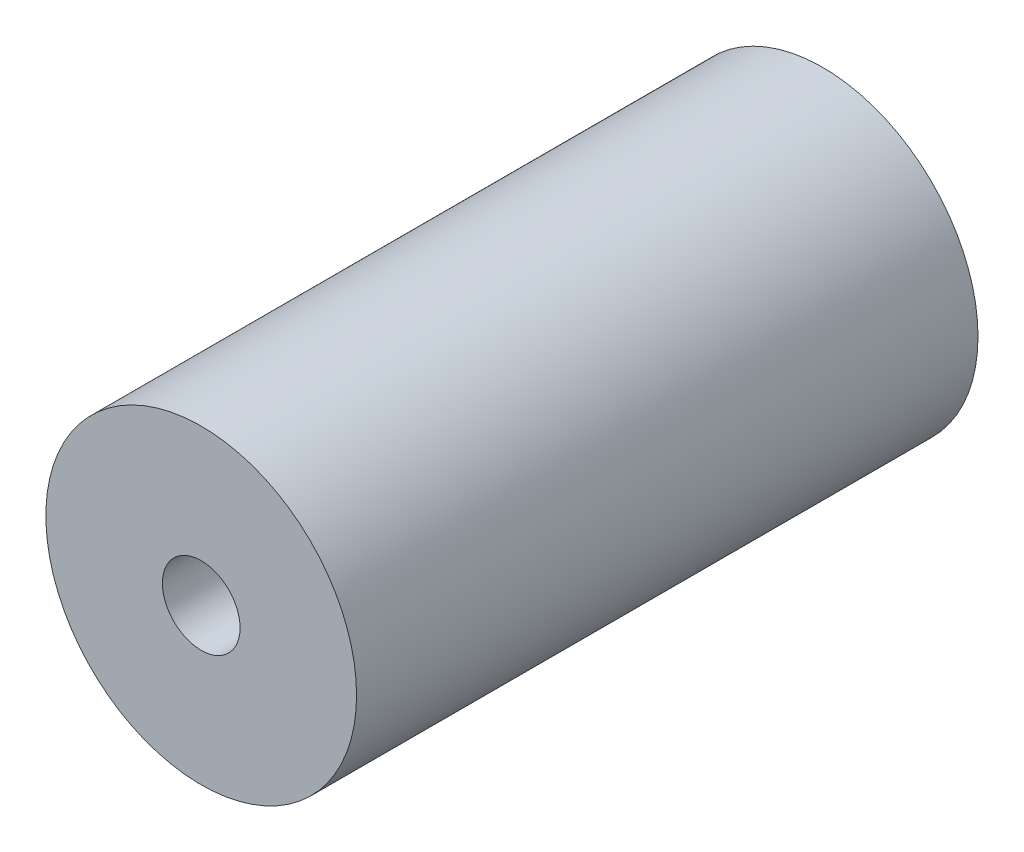
SolidWorks part; units mm, degrees
ref_plane "Front Plane" through (0, 0, 0) normal (0, 0, 1) x (1, 0, 0)
ref_plane "Top Plane" through (0, 0, 0) normal (0, 1, 0) x (1, 0, 0)
ref_plane "Right Plane" through (0, 0, 0) normal (1, 0, 0) x (0, 0, -1)
sketch "Sketch1" plane through (0, 0, 0) normal (0, 0, 1) x (1, 0, 0)
  line L0 (0.8316, -1) -> (1.118, -1) construction
  line L1 (-1.1181, -0.9999) -> (-0.8313, -1) construction
  line L2 (0.8316, -1) -> (-0.8313, -1) construction
  line L3 (0.8316, -1) -> (1.118, -1) construction
  line L4 (-1.1181, -0.9999) -> (-0.8313, -1) construction
  line L5 (0.8316, -1) -> (-0.8313, -1) construction
  line L6 (-1.0724, -0.8999) -> (-0.8313, -0.9)
  line L7 (0.8316, -0.9) -> (-0.8313, -0.9)
  line L8 (0.8316, -0.9) -> (1.0724, -0.9)
  circle A0 centre (0, 0) radius 5
  arc A1 (1.118, -1) -> (-1.5, 0) centre (0, 0) ccw construction
  arc A2 (-1.5, 0) -> (-1.1181, -0.9999) centre (0, 0) ccw construction
  arc A3 (1.118, -1) -> (-1.5, 0) centre (0, 0) ccw construction
  arc A4 (-1.5, 0) -> (-1.1181, -0.9999) centre (0, 0) ccw construction
  arc A5 (1.0724, -0.9) -> (-1.4, 0) centre (0, 0) ccw
  arc A6 (-1.4, 0) -> (-1.0724, -0.8999) centre (0, 0) ccw
  dimension "D1" = 10
  dimension "D2" = 0.1
extrude "Boss-Extrude1" add sketch "Sketch1" along normal blind 10
sketch "Sketch2" plane through (0, 0, 10) normal (0, 0, 1) x (1, 0, 0)
  circle A0 centre (0, 0) radius 1.25
  circle A1 centre (0, 0) radius 5
  dimension "D1" = 2.5
  dimension "D2" = 10
extrude "Boss-Extrude2" add sketch "Sketch2" along normal blind 10
ref_axis "Axis1" through (0, 0, 20) along (0, 0, -1)
